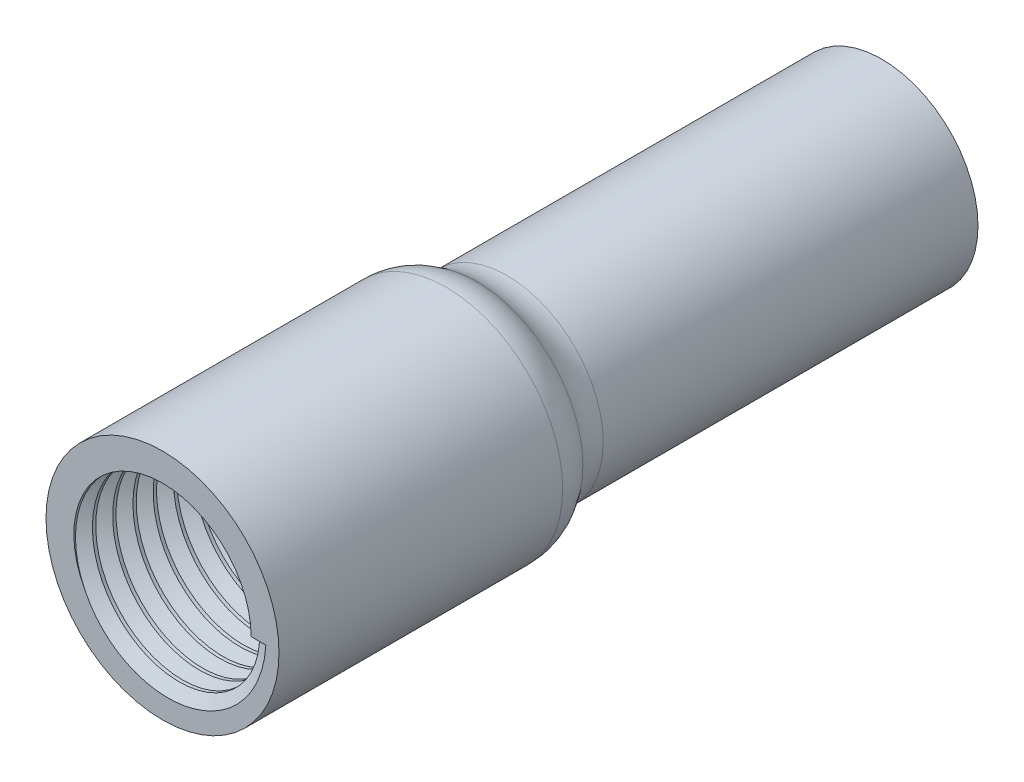
SolidWorks part; units mm, degrees
ref_plane "Front Plane" through (0, 0, 0) normal (0, 0, 1) x (1, 0, 0)
ref_plane "Top Plane" through (0, 0, 0) normal (0, 1, 0) x (1, 0, 0)
ref_plane "Right Plane" through (0, 0, 0) normal (1, 0, 0) x (0, 0, -1)
sketch "Sketch1" plane through (0, 0, 0) normal (0, 0, 1) x (1, 0, 0)
  circle A0 centre (0, 0) radius 6.5
  circle A1 centre (0, 0) radius 9.5
  dimension "D1" = 3
  dimension "D2" = 13
extrude "Boss-Extrude1" add sketch "Sketch1" along normal blind 51
sketch "Sketch6" plane through (0, 0, 51) normal (0, 0, 1) x (1, 0, 0)
  circle A0 centre (0, 0) radius 11.5
  circle A1 centre (0, 0) radius 8.75
  dimension "D1" = 23
  dimension "D2" = 17.5
extrude "Boss-Extrude2" add sketch "Sketch6" along normal blind 20 and the other way blind 10
sketch "Sketch2" plane through (0, 0, 71) normal (0, 0, 1) x (1, 0, 0)
  circle A0 centre (0, 0) radius 9
  dimension "D1" = 18
curve "Helix/Spiral1" pitch 2 height 20 turns 10
sketch "Sketch5" plane through (0, 0, 0) normal (0, 1, 0) x (1, 0, 0)
  line L1 (-11.5, -74.394) -> (11.5, -74.394) construction
  line L2 (-9.5, -70.6135) -> (9.5, -70.6135) construction
  line L3 (-9.5, 0) -> (-9.5, -41) construction
  line L4 (9.5, -41) -> (9.5, 0) construction
  line L5 (7.77, -69.597) -> (7.77, -72.403)
  line L6 (7.77, -72.403) -> (10.2, -71)
  line L8 (10.2, -71) -> (7.77, -69.597)
  line L9 (-11.5, -71) -> (11.5, -71) construction
  line L12 (-11.5, -41) -> (-11.5, -71) construction
  line L13 (11.5, -71) -> (11.5, -41) construction
  line L14 (0, -74.394) -> (0, -71.5957) construction
  point P0 (9.5, -70.9995)
  point P1 (7.77, -71)
  dimension "D1" = 60
  dimension "D2" = 10.2
  dimension "D3" = 7.77
sweep "Cut-Sweep4" cut profiles "Sketch5" path "Helix/Spiral1"
fillet "Fillet2" radius 5 1 edges at (9.5, 0, 41)
fillet "Fillet3" radius 5 1 edges at (11.5, 0, 41)
